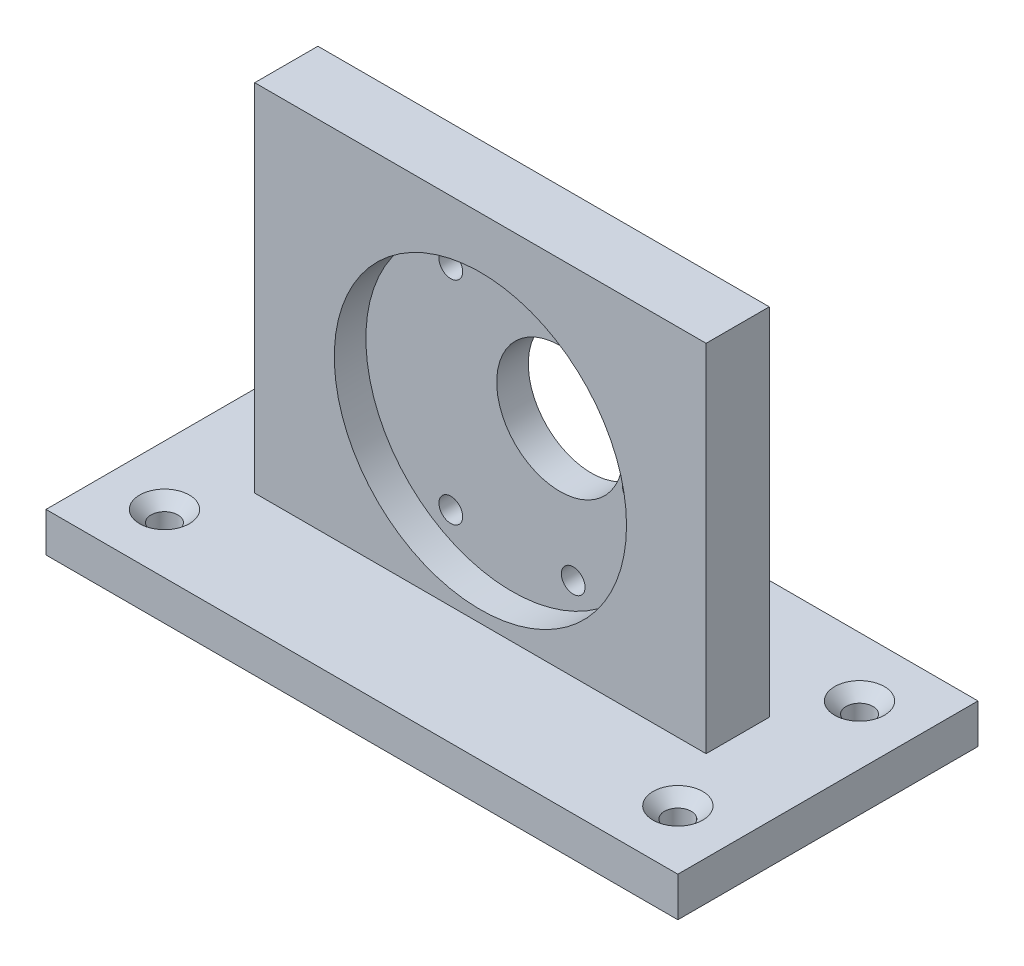
SolidWorks part; units mm, degrees
note: The reader was unsure of these and kept them because the rebuilt part matched: shared geometry of "Sketch3<3>", "Sketch13<2>".
other "Markup1"
sketch "Sketch5" plane through (25, 50, 8) normal (0.9645, 0.1424, 0.2224) x (0.1697, 0.3107, -0.9352)
ref_plane "Front Plane" through (0, 0, 0) normal (0, 0, 1) x (1, 0, 0)
ref_plane "Top Plane" through (0, 0, 0) normal (0, 1, 0) x (1, 0, 0)
ref_plane "Right Plane" through (0, 0, 0) normal (1, 0, 0) x (0, 0, -1)
sketch "Sketch3" plane through (0, 0, 0) normal (0, 0, 1) x (1, 0, 0)
  line L1 (-28.575, 50) -> (28.575, 50)
  line L2 (-28.575, 50) -> (-28.575, 0)
  line L3 (-28.575, 0) -> (28.575, 0)
  line L4 (28.575, 50) -> (28.575, 0)
  line L5 (-7.75, 38.4234) -> (7.75, 38.4234) construction
  line L6 (7.75, 38.4234) -> (15.5, 25) construction
  line L7 (15.5, 25) -> (7.75, 11.5766) construction
  line L8 (7.75, 11.5766) -> (-7.75, 11.5766) construction
  line L9 (-7.75, 11.5766) -> (-15.5, 25) construction
  line L10 (-15.5, 25) -> (-7.75, 38.4234) construction
  line L12 (-20.1843, 13.3466) -> (22.8058, 38.167) construction
  circle A5 centre (-7.75, 38.4234) radius 1.5
  circle A6 centre (7.75, 38.4234) radius 1.5
  circle A8 centre (-7.75, 11.5766) radius 1.5
  circle A9 centre (7.75, 11.5766) radius 1.5
  circle A10 centre (15.5, 25) radius 1.5
  circle A11 centre (6.0622, 28.5) radius 8
  point P4 (0, 0)
  point P27 (-11.625, 18.2883)
  point P28 (11.625, 31.7117)
  dimension "D4" = 25
  dimension "D9" = 16
  dimension "D3" = 3
  dimension "D1" = 50
  dimension "D2" = 57.15
  dimension "D6" = 120
  dimension "D7" = 120
  dimension "D8" = 15.5
  dimension "D10" = 6.4234
extrude "Boss-Extrude1" add sketch "Sketch3" along normal blind 8 contours L2 L3 L4 L1
extrude "Cut-Extrude2" cut sketch "Sketch3<3>" along normal blind 10
sketch "Sketch3<3>" plane through (0, 0, 0) normal (0, 0, 1) x (1, 0, 0) same geometry as "Sketch3"
sketch "Sketch4" plane through (0, 0, 8) normal (0, 0, 1) x (1, 0, 0)
  line L0 (-15.5, 25) -> (15.5, 25) construction
  circle A0 centre (0, 25) radius 18.5
  dimension "D1" = 37
extrude "Cut-Extrude3" cut sketch "Sketch4" against normal blind 4 contours A0
sketch "Sketch6" plane through (0, 0, 8) normal (0, 0, 1) x (1, 0, 0)
  line L1 (-40, 5) -> (40, 5)
  line L2 (-40, 5) -> (-40, 0)
  line L3 (-40, 0) -> (40, 0)
  line L4 (40, 5) -> (40, 0)
  point P4 (0, 0)
  dimension "D1" = 80
  dimension "D2" = 5
extrude "Boss-Extrude2" add sketch "Sketch6" against normal blind 23 and the other way blind 15
sketch "Sketch7" plane through (0, 5, 0) normal (0, 1, 0) x (1, 0, 0)
  line L0 (-40, -23) -> (-40, 15) construction
  line L1 (-40, -23) -> (-32.5, -23)
  line L2 (-40, -23) -> (-40, -15.5)
  line L3 (-40, -15.5) -> (-32.5, -15.5)
  line L4 (-32.5, -23) -> (-32.5, -15.5)
  line L5 (-40, -4) -> (40, -4) construction
  line L6 (40, -23) -> (40, 15) construction
  line L7 (0, 15) -> (0, -23) construction
  line L8 (40, 15) -> (-40, 15) construction
  line L9 (40, -23) -> (-40, -23) construction
  point P18 (-32.5, 7.5)
  point P20 (32.5, -15.5)
  point P21 (32.5, 7.5)
  dimension "D1" = 7.5
hole_wizard "CSK for M3 Flat Head Machine Screw1" positions "Sketch8" profile "Sketch9" countersink size "M3" standard "ANSI Metric" end condition through all
sketch "Sketch8" plane through (0, 5, 0) normal (0, 1, 0) x (1, 0, 0)
  point P0 (-32.5, 7.5)
  point P3 (-32.5, -15.5)
  point P6 (32.5, -15.5)
  point P9 (32.5, 7.5)
sketch "Sketch9" plane through (-32.5, 5, -7.5) normal (1, 0, 0) x (0, 0, 1)
  line L0 (0, 0) -> (0, 5)
  line L1 (0, 5) -> (1.7, 5)
  line L2 (1.7, 5) -> (1.7, 1.45)
  line L3 (1.7, 1.45) -> (3.15, 0)
  line L5 (3.15, 0) -> (0, 0)
  line L6 (-1.7, 1.45) -> (-3.15, 0) construction
  line L11 (0, -6.35) -> (0, 107.95) construction
  dimension "Thru Hole Dia." = 3.4
  dimension "Thru Hole Depth" = 5
  dimension "Near C'Sink Dia." = 6.3
  dimension "Near C'Sink Angle" = 90
sketch "Sketch13" plane through (0, 0, 0) normal (0, 0, -1) x (-1, 0, 0)
  line L0 (20.3378, 28.5) -> (-6.0622, 28.5) construction
  circle A5 centre (20.3378, 28.5) radius 5.334
  circle A7 centre (20.3378, 28.5) radius 7.239
  dimension "D1" = 10.668
  dimension "D2" = 1.905
  dimension "D3" = 26.4
extrude "Boss-Extrude4" add sketch "Sketch13" along normal blind 2.54
extrude "Cut-Extrude6" cut sketch "Sketch16" against normal up to surface (4.826 mm away)
sketch "Sketch16" plane through (-499.2489, 16.8212, -28.3089) normal (0.0361, 0.9993, -0.0009) x (0.0508, -0.0009, 0.9987)
  circle A0 centre (67.5, 464.5) radius 1.7
  circle A2 centre (92.5, 462.5) radius 1.8
  circle A3 centre (113.4, 462.5) radius 1.8
  circle A4 centre (92.5, 401.5) radius 1.8
  circle A5 centre (113.4, 401.5) radius 1.8
  circle A7 centre (67.5, 399.5) radius 1.7
  circle A8 centre (44.5, 399.5) radius 1.7
  circle A9 centre (33.5, 468.8378) radius 1.7
  circle A10 centre (33.5, 435.8378) radius 1.7
  circle A11 centre (44.5, 464.5) radius 1.7
extrude "Cut-Extrude7" cut sketch "Sketch13<2>" against normal blind 3.175
sketch "Sketch13<2>" plane through (0, 0, 0) normal (0, 0, -1) x (-1, 0, 0) same geometry as "Sketch13"
